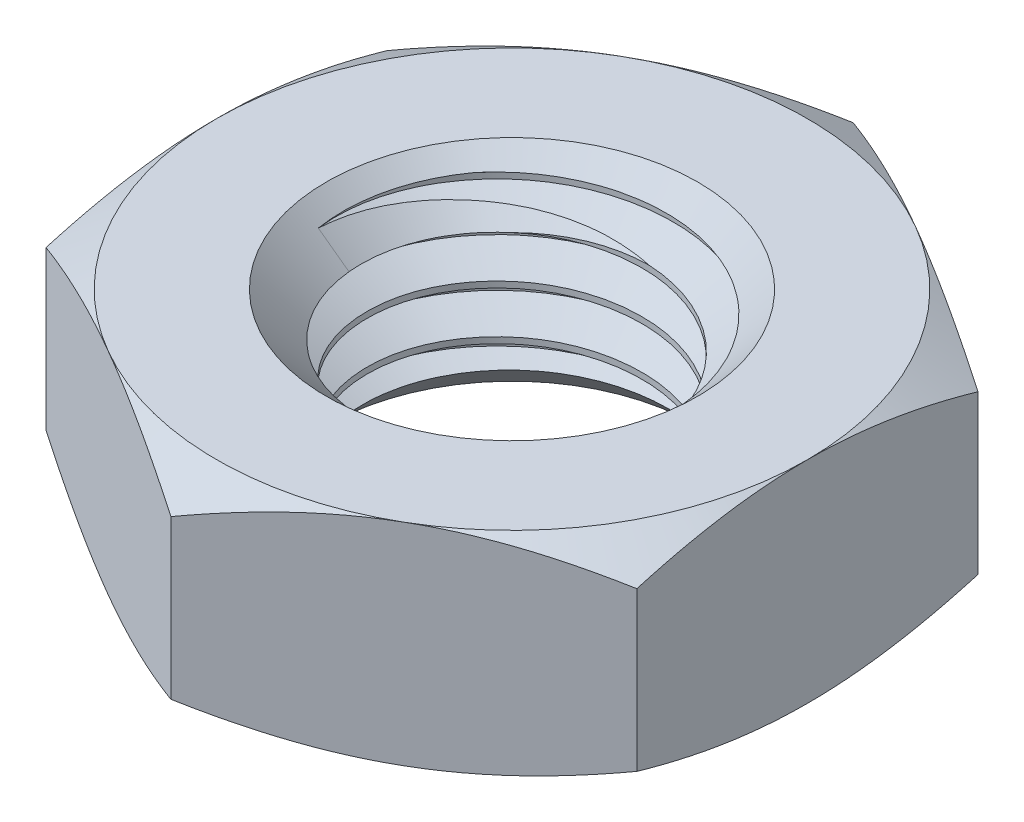
SolidWorks part; units mm, degrees
ref_plane "Front Plane" through (0, 0, 0) normal (0, 0, 1) x (1, 0, 0)
ref_plane "Top Plane" through (0, 0, 0) normal (0, 1, 0) x (1, 0, 0)
ref_plane "Right Plane" through (0, 0, 0) normal (1, 0, 0) x (0, 0, -1)
sketch "Sketch1" plane through (0, 0, 0) normal (0, 0, 1) x (1, 0, 0)
  line L0 (0, -1.9844) -> (0, 1.9844) construction
  line L1 (3.175, 1.9844) -> (-3.175, 1.9844) construction
  line L2 (-5.5562, -1.9844) -> (5.5562, -1.9844) construction
  line L3 (3.175, 1.9844) -> (3.175, 1.0772) construction
  point P4 (0, 0)
  point P8 (0, 1.9844)
  point P10 (0, -1.9844)
  dimension "Height" = 3.9688
  dimension "Width" = 11.1125
  dimension "Thread Dia" = 6.35
  dimension "Pitch" = 0.9071
sketch "Sketch2" plane through (0, 0, 0) normal (0, 1, 0) x (1, 0, 0)
  line L1 (0, 6.4158) -> (-5.5562, 3.2079)
  line L2 (-5.5562, 3.2079) -> (-5.5562, -3.2079)
  line L3 (-5.5562, -3.2079) -> (0, -6.4158)
  line L4 (0, -6.4158) -> (5.5562, -3.2079)
  line L5 (5.5562, -3.2079) -> (5.5562, 3.2079)
  line L6 (5.5562, 3.2079) -> (0, 6.4158)
  circle A0 centre (0, 0) radius 5.5562 construction
  circle A1 centre (0, 0) radius 3.175
  point P11 (0, -3.175)
  point P14 (0, 0)
extrude "Boss-Extrude1" add sketch "Sketch2" along normal up to vertex (1.9844 mm away) and the other way up to vertex (1.9844 mm away) up to point (0, 1.9844, 0) other way up to point (0, -1.9844, 0)
sketch "Sketch3" plane through (0, 0, 0) normal (1, 0, 0) x (0, 0, -1)
  line L0 (-6.4158, 1.4881) -> (-5.5562, 1.9844)
  line L1 (-6.4158, 1.9844) -> (-6.4158, -1.9844) construction
  line L2 (-6.4158, 1.9844) -> (-3.2079, 1.9844) construction
  line L3 (-6.4158, -1.4881) -> (-5.5562, -1.9844)
  line L4 (-6.4158, -1.9844) -> (-3.2079, -1.9844) construction
  line L5 (-6.4158, 1.4881) -> (-6.4158, 1.9844)
  line L6 (-6.4158, 1.9844) -> (-5.5562, 1.9844)
  line L7 (-6.4158, -1.4881) -> (-6.4158, -1.9844)
  line L8 (-6.4158, -1.9844) -> (-5.5562, -1.9844)
  line L9 (-5.5562, 1.9844) -> (-5.5562, -1.9844) construction
  line L10 (-3.4925, 1.9844) -> (-3.175, 1.9844)
  line L11 (-3.2079, 1.9844) -> (3.2079, 1.9844) construction
  line L12 (-3.175, 1.9844) -> (-3.175, 1.6669)
  line L13 (-3.175, 1.6669) -> (-3.4925, 1.9844)
  line L14 (-3.4925, -1.9844) -> (-3.175, -1.9844)
  line L15 (-3.2079, -1.9844) -> (3.2079, -1.9844) construction
  line L16 (-3.175, -1.9844) -> (-3.175, -1.6669)
  line L17 (-3.4925, -1.9844) -> (-3.175, -1.6669)
  line L18 (-3.175, 1.6669) -> (-3.175, -1.6669) construction
  line L19 (3.175, 0) -> (-3.175, 0) construction
  line L22 (0, 1.9844) -> (0, -1.9844) construction
  point P15 (-5.5562, 0)
  point P24 (-3.175, 0)
  dimension "D1" = 30
  dimension "D2" = 3.4925
revolve "Cut-Revolve1" cut sketch "Sketch3" angle 360 about L22
sketch "Sketch4" plane through (0, 1.9844, 0) normal (0, 1, 0) x (1, 0, 0)
  circle A0 centre (0, 0) radius 3.175 construction
  circle A1 centre (0, 0) radius 3.175
extrude "Boss-Extrude2" add sketch "Sketch4" against normal up to surface (3.9688 mm away) separate body up to face at (0, -1.9844, 3.4925)
sketch "Sketch5" plane through (0, 1.9844, 0) normal (0, 1, 0) x (1, 0, 0)
  circle A0 centre (0, 0) radius 3.175 construction
  circle A1 centre (0, 0) radius 3.175
curve "Helix/Spiral1" pitch 0.9071 height 4.8759 radius 3.175 centre (0, 1.9844, 0) axis (0, -1, 0) start towards (0, 0, 1)
sketch "Sketch6" plane through (0, 0, 0) normal (1, 0, 0) x (0, 0, -1)
  line L0 (-3.2732, 1.9277) -> (-2.4876, 2.3812) construction
  line L1 (-2.4876, 2.3812) -> (-3.2732, 2.8348) construction
  line L2 (-3.2732, 2.8348) -> (-3.2732, 1.9277) construction
  line L3 (-2.5858, 2.4379) -> (-2.5858, 2.3246) construction
  line L4 (-3.175, 2.7781) -> (-3.175, 1.9844) construction
  line L5 (-3.2732, 2.3812) -> (-3.175, 2.3812) construction
  line L6 (-2.5858, 2.3812) -> (-2.4876, 2.3812) construction
  line L7 (-3.2241, 2.3812) -> (-3.2241, 1.956) construction
  line L8 (-3.2241, 1.956) -> (-3.2241, 2.8065)
  line L9 (-3.2241, 2.8065) -> (-2.5858, 2.4379)
  line L10 (-2.5858, 2.4379) -> (-2.5858, 2.3246)
  line L11 (-2.5858, 2.3246) -> (-3.2241, 1.956)
  dimension "D1" = 0.9071
  dimension "D2" = 0.1134
sweep "Cut-Sweep1" cut profiles "Sketch6" path "Helix/Spiral1" align with end faces yes
sketch "Sketch7" plane through (0, 0, 0) normal (1, 0, 0) x (0, 0, -1)
  line L0 (-3.4925, 1.9844) -> (-1.905, 0.3969)
  line L2 (-3.4925, 1.9844) -> (0, 1.9844)
  line L3 (-3.4925, 1.9844) -> (-3.175, 1.9844) construction
  line L4 (-3.4925, -1.9844) -> (0, -1.9844)
  line L5 (-3.4925, -1.9844) -> (-3.175, -1.9844) construction
  line L6 (-3.4925, -1.9844) -> (-1.905, -0.3969)
  line L7 (-3.4925, -1.9844) -> (-3.175, -1.6669) construction
  line L8 (0, -1.9844) -> (0, 1.9844) construction
  line L9 (0, -1.9844) -> (0, 1.9844) construction
  line L12 (-1.905, 0.3969) -> (0, 0.3969)
  line L13 (0, 0.3969) -> (0, 1.9844)
  line L14 (-3.175, 1.6669) -> (-3.4925, 1.9844) construction
  line L15 (-1.905, -0.3969) -> (0, -0.3969)
  line L16 (0, -0.3969) -> (0, -1.9844)
  dimension "D1" = 1.905
revolve "Revolve1" add sketch "Sketch7" angle 360 about L9
sketch "Sketch8" plane through (0, 1.9844, 0) normal (0, 1, 0) x (1, 0, 0)
  circle A0 centre (0, 0) radius 3.4925 construction
  circle A1 centre (0, 0) radius 3.4925
extrude "Boss-Extrude3" add sketch "Sketch8" against normal up to surface (3.9688 mm away) up to face at (0, -1.9844, 3.4925)
combine bodies "Combine1" operation type subtract main body 109 bodies to subtract 108
equation "\"D2@Sketch3\"=\"Thread Dia@Sketch1\"*.55"
equation "\"D4@Helix/Spiral1\"=\"Pitch@Sketch1\""
equation "\"D3@Helix/Spiral1\"=\"Height@Sketch1\"+\"Pitch@Sketch1\""
equation "\"D1@Sketch6\"=\"Pitch@Sketch1\""
equation "\"D2@Sketch6\"=\"Pitch@Sketch1\"/8"
equation "\"D1@Sketch7\"=\"Thread Dia@Sketch1\"*.3"
